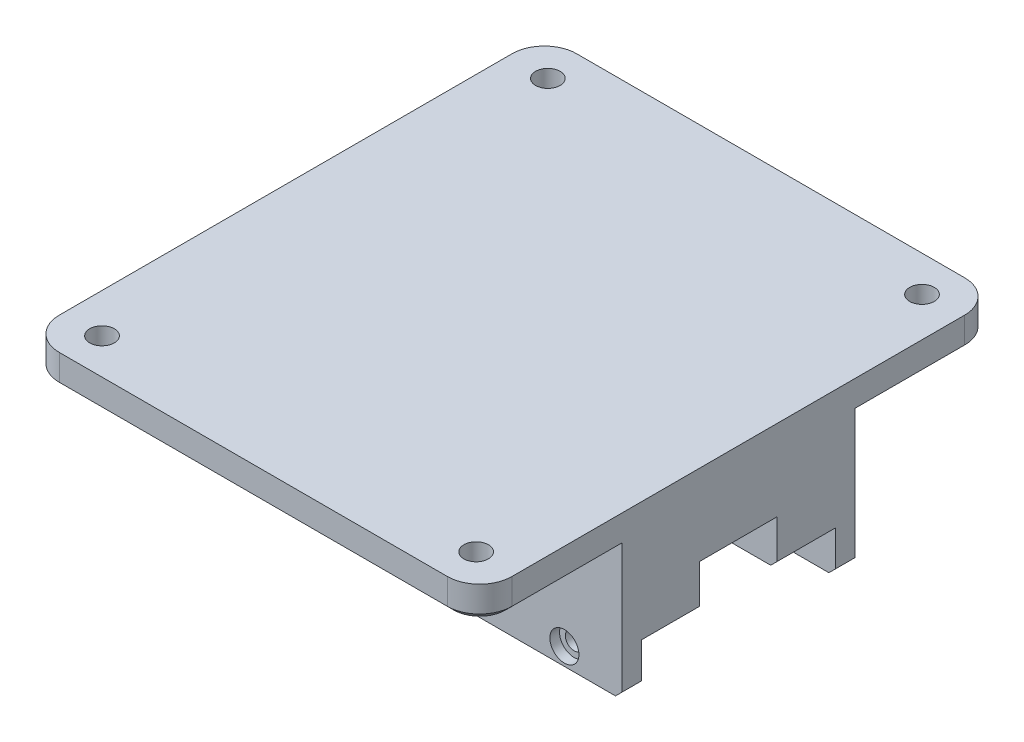
SolidWorks part; units mm, degrees
ref_plane "Front Plane" through (0, 0, 0) normal (0, 0, 1) x (1, 0, 0)
ref_plane "Top Plane" through (0, 0, 0) normal (0, 1, 0) x (1, 0, 0)
ref_plane "Right Plane" through (0, 0, 0) normal (1, 0, 0) x (0, 0, -1)
sketch "Sketch1" plane through (0, 0, 0) normal (0, 0, 1) x (1, 0, 0)
  line L8 (-9.1, 2.5) -> (25.9, 2.5) construction
  line L14 (25.9, 17.3) -> (-9.1, 17.3)
  line L15 (-9.1, 2.5) -> (-9.1, -2.7) construction
  line L16 (-9.1, -2.7) -> (25.9, -2.7)
  line L21 (25.9, 2.5) -> (25.9, -2.7)
  line L26 (-9.1, 17.3) -> (-44.1, 17.3)
  line L27 (-17, -50.9163) -> (-17, 49949.0837) construction
  line L29 (25.9, 17.3) -> (25.9, 2.5)
  line L30 (0, 0) -> (17, 0) construction
  line L32 (-9.1, 2.5) -> (-9.1, 17.3) construction
  line L33 (-44.1, 17.3) -> (-44.1, -2.7)
  line L34 (-44.1, -2.7) -> (-9.1, -2.7)
  line L35 (0, 0) -> (-47.3083, 0) construction
  circle A10 centre (0, 0) radius 1.35 construction
  circle A11 centre (17, 0) radius 1.35 construction
  circle A15 centre (-35.2, 0) radius 1.35 construction
  circle A16 centre (-18.2, 0) radius 1.35 construction
  dimension "D2" = 9.1
  dimension "D3" = 17
  dimension "D4" = 35
  dimension "D6" = 20
  dimension "D7" = 17
  dimension "D8" = 9.1
  dimension "D9" = 2.7
  dimension "D12" = 2.7
  dimension "D5" = 5.2
extrude "Boss-Extrude1" add sketch "Sketch1" along normal blind 18
sketch "Croquis2" plane through (0, 0, 18) normal (0, 0, 1) x (1, 0, 0)
  circle A0 centre (0, 0) radius 1.35
  circle A1 centre (17, 0) radius 1.35
  circle A3 centre (-18.2, 0) radius 1.35
  circle A4 centre (-35.2, 0) radius 1.35
extrude "Cortar-Extruir2" cut sketch "Croquis2" against normal blind 5
sketch "Sketch3" plane through (0, 0, 18) normal (0, 0, 1) x (1, 0, 0)
  circle A5 centre (0, 0) radius 2.25
  circle A6 centre (17, 0) radius 2.25
  circle A8 centre (-18.2, 0) radius 2.25
  circle A9 centre (-35.2, 0) radius 2.25
extrude "Cut-Extrude1" cut sketch "Sketch3" against normal blind 1.5
sketch "Croquis3" plane through (0, 0, 18) normal (0, 0, -1) x (-1, 0, 0)
  line L0 (-25.9, -2.7) -> (-25.9, 2.8)
  line L2 (-25.9, 2.8) -> (4.1, 2.8)
  line L4 (44.1, -2.7) -> (-25.9, -2.7)
  line L5 (9.1, -2.7) -> (-25.9, -2.7) construction
  line L6 (-25.9, -2.7) -> (-25.9, 17.3) construction
  line L7 (44.1, -2.7) -> (-25.9, -2.7) construction
  line L8 (44.1, -2.7) -> (44.1, 2.8)
  line L10 (44.1, 2.8) -> (14.1, 2.8)
  line L11 (14.1, 2.8) -> (9.1, -2.2)
  line L13 (9.1, -2.2) -> (4.1, 2.8)
  line L14 (9.1, 2.5) -> (9.1, -2.7) construction
  dimension "D1" = 45
  dimension "D2" = 45
  dimension "D3" = 0.5
  dimension "D4" = 5.5
extrude "Cortar-Extruir3" cut sketch "Croquis3" along normal blind 17 from offset 3
mirror "Mirror1" about plane through (0, 0, 0) normal (0, 0, -1) of "Cortar-Extruir3", "Cortar-Extruir2", "Boss-Extrude1", "Cut-Extrude1"
sketch "Croquis4" plane through (0, 2.8, 0) normal (0, -1, 0) x (1, 0, 0)
  line L1 (-44.1, 6) -> (25.9, 6)
  line L2 (-44.1, 6) -> (-44.1, -6)
  line L3 (-44.1, -6) -> (25.9, -6)
  line L4 (25.9, 6) -> (25.9, -6)
  line L5 (25.9, -15) -> (25.9, 15) construction
  line L6 (-44.1, -15) -> (-44.1, 15) construction
  line L7 (-9.1, 0) -> (-44.1, 0) construction
  point P10 (-44.1, 0)
  dimension "D1" = 6
extrude "Cortar-Extruir4" cut sketch "Croquis4" along normal through all and the other way blind 6
sketch "Croquis5" plane through (0, 0, 18) normal (0, 0, 1) x (1, 0, 0)
  line L1 (-13.1, 10.6716) -> (-13.1, 16.3)
  line L3 (-13.1, 16.3) -> (-5.1, 16.3)
  line L5 (-5.1, 16.3) -> (-5.1, 11.3)
  line L6 (-13.1, 6.3) -> (-5.1, 6.3)
  line L7 (-5.1, 6.3) -> (-5.1, 11.3)
  line L8 (-13.1, 6.3) -> (-13.1, 10.6716)
  line L9 (-9.1, 2.5) -> (-9.1, 17.3) construction
  line L10 (25.9, 17.3) -> (-9.1, 17.3) construction
  point P4 (-9.1, 16.3)
  dimension "D1" = 10
  dimension "D2" = 5
  dimension "D3" = 8
  dimension "D4" = 1
extrude "Cortar-Extruir11" cut sketch "Croquis5" against normal through all
sketch "Croquis6" plane through (0, 17.3, 0) normal (0, 1, 0) x (1, 0, 0)
  line L0 (-9.1, 0) -> (-25.7361, 0) construction
  line L1 (-9.1, 0) -> (-9.1, -45) construction
  line L2 (-38.0254, -34.472) -> (-9.1, 0) construction
  line L4 (-44.1, 40) -> (25.9, 40)
  line L5 (-44.1, 18) -> (25.9, -18) construction
  line L6 (-44.1, -18) -> (25.9, 18) construction
  line L7 (-44.1, 40) -> (-44.1, -40)
  line L8 (-44.1, -40) -> (25.9, -40)
  line L9 (25.9, 40) -> (25.9, -40)
  line L10 (-44.1, 40) -> (25.9, -40) construction
  line L11 (-44.1, -40) -> (25.9, 40) construction
  arc A0 (-38.0254, -34.472) -> (22.8572, -31.6818) centre (-9.1, 0) ccw construction
  circle A1 centre (-38.0254, -34.472) radius 1.9
  circle A2 centre (19.8254, -34.472) radius 1.9
  circle A3 centre (19.8254, 34.472) radius 1.9
  circle A4 centre (-38.0254, 34.472) radius 1.9
  point P14 (-9.1, 0)
  dimension "D2" = 3.8
  dimension "D1" = 45
  dimension "D3" = 40
  dimension "D4" = 80
extrude "Saliente-Extruir1" add sketch "Croquis6" along normal blind 5
fillet "Redondeo1" radius 5 4 edges at (25.9, 19.8, 40) (-44.1, 19.8, 40) (25.9, 19.8, -40) (-44.1, 19.8, -40)
fillet "Redondeo2" [suppressed] radius 1
chamfer "Chaflán1" distance 1 angle 45 4 edges at (-9.1, 6.3, 18) (-13.1, 11.3, 18) (-9.1, 16.3, 18) (-5.1, 11.3, 18)
chamfer "Chaflán2" distance 1 angle 45 4 edges at (-5.1, 11.3, -18) (-9.1, 6.3, -18) (-13.1, 11.3, -18) (-9.1, 16.3, -18)
chamfer "Chaflán3" distance 1 angle 45 10 edges at (-44.1, 17.3, 26.5) (25.9, 17.3, 26.5) (-42.6355, 17.3, 38.5355) (24.4355, 17.3, 38.5355) (-9.1, 17.3, 40) (25.9, 17.3, -26.5) (-44.1, 17.3, -26.5) (24.4355, 17.3, -38.5355) (-42.6355, 17.3, -38.5355) (-9.1, 17.3, -40)
chamfer "Chaflán5" distance 1 angle 45 10 edges at (25.9, -2.7, -16.5) (-44.1, -2.7, 16.5) (25.9, -2.7, 16.5) (25.9, 2.8, 10.5) (-44.1, 2.8, 10.5) (-44.1, 8.8, 0) (25.9, 8.8, 0) (-44.1, 2.8, -10.5) (25.9, 2.8, -10.5) (-44.1, -2.7, -16.5)
chamfer "Chaflán6" distance 2 angle 45 4 edges at (10.4, 17.3, -18) (-28.6, 17.3, -18) (10.4, 17.3, 18) (-28.6, 17.3, 18)
